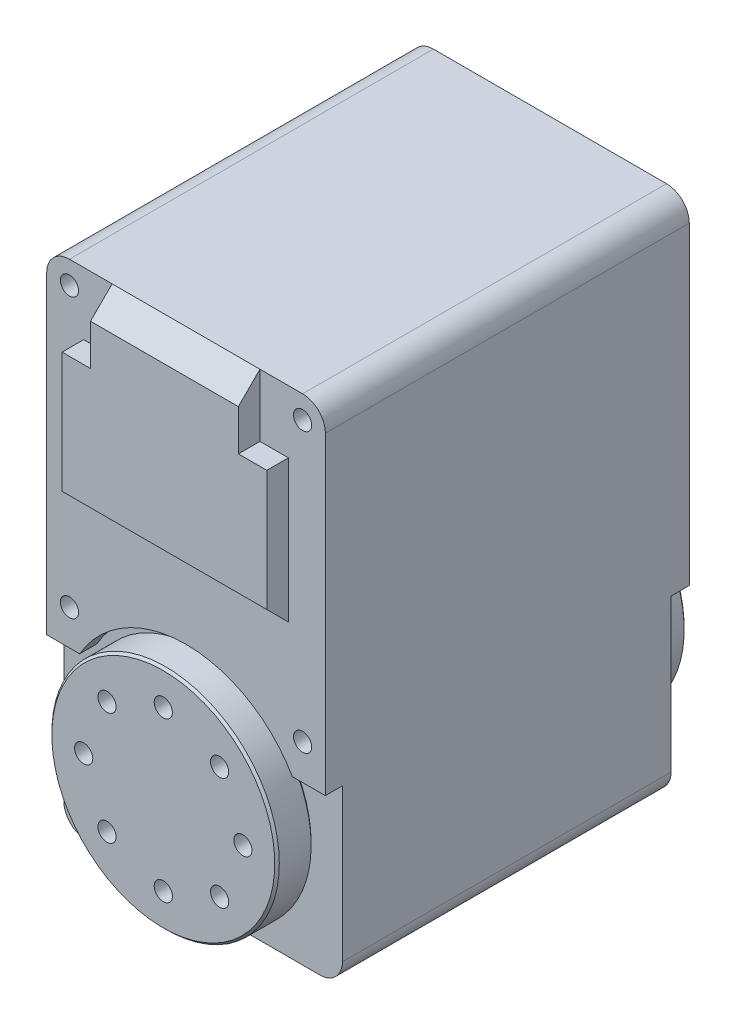
SolidWorks part; units mm, degrees
ref_plane "Front Plane" through (0, 0, 0) normal (0, 0, 1) x (1, 0, 0)
ref_plane "Top Plane" through (0, 0, 0) normal (0, 1, 0) x (1, 0, 0)
ref_plane "Right Plane" through (0, 0, 0) normal (1, 0, 0) x (0, 0, -1)
sketch "Sketch1" plane through (0, 0, 0) normal (0, 0, 1) x (1, 0, 0)
  line L1 (-10.25, 22.5) -> (10.25, 22.5)
  line L2 (-12.25, 20.5) -> (-12.25, -20.5)
  line L3 (-10.25, -22.5) -> (10.25, -22.5)
  line L4 (12.25, 20.5) -> (12.25, -20.5)
  line L5 (-12.25, 22.5) -> (12.25, -22.5) construction
  line L6 (-12.25, -22.5) -> (12.25, 22.5) construction
  arc A0 (10.25, -22.5) -> (12.25, -20.5) centre (10.25, -20.5) ccw
  arc A1 (-10.25, -22.5) -> (-12.25, -20.5) centre (-10.25, -20.5) cw
  arc A2 (12.25, 20.5) -> (10.25, 22.5) centre (10.25, 20.5) ccw
  arc A3 (-12.25, 20.5) -> (-10.25, 22.5) centre (-10.25, 20.5) cw
  point P0 (0, 0)
  dimension "D3" = 2
  dimension "D1" = 24.5
  dimension "D2" = 45
extrude "Boss-Extrude1" add sketch "Sketch1" along normal blind 32
sketch "Sketch2" plane through (0, 0, 32) normal (0, 0, 1) x (1, 0, 0)
  line L0 (-10.25, -22.5) -> (10.25, -22.5) construction
  line L1 (12.25, -20.5) -> (12.25, 20.5) construction
  line L2 (-12.25, 20.5) -> (-12.25, -20.5) construction
  line L3 (-12.25, -7.1) -> (12.25, -7.1)
  line L4 (-12.25, -7.1) -> (-12.25, -22.5)
  line L5 (-12.25, -22.5) -> (12.25, -22.5)
  line L6 (12.25, -7.1) -> (12.25, -22.5)
  circle A0 centre (0, -12.5) radius 10.8
  arc M5 (10.25, -22.5) -> (12.25, -20.5) centre (10.25, -20.5) ccw
  line M6 (12.25, -20.5) -> (12.25, 20.5)
  line M10 (-12.25, 20.5) -> (-12.25, -20.5)
  arc M11 (-12.25, -20.5) -> (-10.25, -22.5) centre (-10.25, -20.5) ccw
  line M12 (-10.25, -22.5) -> (10.25, -22.5)
  dimension "D1" = 21.6
  dimension "D2" = 10
  dimension "D3" = 12.25
  dimension "D4" = 0
  dimension "D5" = 0
  dimension "D6" = 15.4
extrude "Cut-Extrude1" cut sketch "Sketch2" against normal blind 1.5 contours L3 A0 | L3 A0 L5 | A0 L3 M12 M5 M6 | A0 L3 M10 M11 M12 region at (-10.3353, -16.6231, 32) region at (0, -4.8858, 32) region at (0, -14.2224, 32) region at (10.3353, -16.6231, 32)
sketch "Sketch3" plane through (0, 0, 0) normal (0, 0, -1) x (-1, 0, 0)
  line L0 (10.25, -22.5) -> (-10.25, -22.5) construction
  line L1 (12.25, 20.5) -> (12.25, -20.5) construction
  line L3 (-12.25, -7.1) -> (12.25, -7.1)
  line L4 (-12.25, -7.1) -> (-12.25, -22.5)
  line L5 (-12.25, -22.5) -> (12.25, -22.5)
  line L6 (12.25, -7.1) -> (12.25, -22.5)
  circle A0 centre (0, -12.5) radius 10.8
  dimension "D1" = 21.6
  dimension "D2" = 10
  dimension "D3" = 12.25
  dimension "D4" = 0
  dimension "D5" = 0
extrude "Cut-Extrude2" cut sketch "Sketch3" against normal blind 1.6 contours L3 A0 | L3 A0 L5 | L4 L5 L6 L3 region at (0, -4.8858, 0) region at (0, -14.2224, 0)
sketch "Sketch4" plane through (0, 0, 30.5) normal (0, 0, 1) x (1, 0, 0)
  circle A0 centre (0, -12.5) radius 3.2
  dimension "D1" = 6.4
extrude "Boss-Extrude2" add sketch "Sketch4" along normal blind 0.3 and the other way blind 29.3
sketch "Sketch5" plane through (0, 0, 30.8) normal (0, 0, 1) x (1, 0, 0)
  line L0 (12.25, -20.5) -> (12.25, -7.1) construction
  circle A0 centre (0, -12.5) radius 10
  circle A1 centre (0, -5.5) radius 0.8
  circle A2 centre (4.9497, -7.5503) radius 0.8
  circle A3 centre (7, -12.5) radius 0.8
  circle A4 centre (4.9497, -17.4497) radius 0.8
  circle A5 centre (0, -19.5) radius 0.8
  circle A6 centre (-4.9497, -17.4497) radius 0.8
  circle A7 centre (-7, -12.5) radius 0.8
  circle A8 centre (-4.9497, -7.5503) radius 0.8
  point P24 (0, -12.5)
  dimension "D1" = 20
  dimension "D2" = 1.6
  dimension "D3" = 7
  dimension "D6" = 7
  dimension "D7" = 7
  dimension "D4" = 12.25
  dimension "D5" = 8
extrude "Boss-Extrude3" add sketch "Sketch5" along normal blind 3.2
sketch "Sketch6" plane through (0, 0, 1.2) normal (0, 0, -1) x (-1, 0, 0)
  line L0 (12.25, 20.5) -> (12.25, -7.1) construction
  circle A0 centre (0, -12.5) radius 10
  circle A1 centre (0, -5.5) radius 0.8
  circle A2 centre (4.9497, -7.5503) radius 0.8
  circle A3 centre (7, -12.5) radius 0.8
  circle A4 centre (4.9497, -17.4497) radius 0.8
  circle A5 centre (0, -19.5) radius 0.8
  circle A6 centre (-4.9497, -17.4497) radius 0.8
  circle A7 centre (-7, -12.5) radius 0.8
  circle A8 centre (-4.9497, -7.5503) radius 0.8
  point P23 (0, -12.5)
  dimension "D1" = 20
  dimension "D2" = 1.6
  dimension "D3" = 7
  dimension "D4" = 12.25
  dimension "D5" = 8
extrude "Boss-Extrude5" add sketch "Sketch6" along normal blind 3.2
sketch "Sketch7" plane through (0, 0, 32) normal (0, 0, 1) x (1, 0, 0)
  line L0 (10.25, 22.5) -> (-10.25, 22.5) construction
  line L1 (-9, 22.5) -> (9, 22.5)
  line L2 (-9, 22.5) -> (-9, 4.5)
  line L3 (-9, 4.5) -> (9, 4.5)
  line L4 (9, 22.5) -> (9, 4.5)
  line L6 (-9, 22.5) -> (-6.5, 22.5)
  line L7 (-9, 22.5) -> (-9, 17)
  line L8 (-9, 17) -> (-6.5, 17)
  line L9 (-6.5, 22.5) -> (-6.5, 17)
  line L10 (9, 22.5) -> (6.5, 22.5)
  line L11 (9, 22.5) -> (9, 17)
  line L12 (9, 17) -> (6.5, 17)
  line L13 (6.5, 22.5) -> (6.5, 17)
  dimension "D1" = 18
  dimension "D2" = 9
  dimension "D3" = 18
  dimension "D4" = 5.5
  dimension "D5" = 5.5
  dimension "D6" = 2.5
  dimension "D7" = 2.5
extrude "Boss-Extrude6" add sketch "Sketch7" along normal blind 1.9 contours L13 L1 L9 L8 L2 L3 L4 L12 region at (0, 12.9203, 32)
chamfer "Chamfer1" distance 1.9 angle 45 2 edges at (0, 22.5, 33.9) (0, 4.5, 33.9)
sketch "Sketch8" plane through (0, 0, 0) normal (0, 0, -1) x (-1, 0, 0)
  line L0 (-10.25, 22.5) -> (10.25, 22.5) construction
  line L1 (-7, 22.5) -> (7, 22.5)
  line L2 (-7, 22.5) -> (-7, -7.5)
  line L3 (-7, -7.5) -> (7, -7.5)
  line L4 (7, 22.5) -> (7, -7.5)
  circle A0 centre (0, -12.5) radius 10.8
  arc M4 (-9.3531, -7.1) -> (9.3531, -7.1) centre (0, -12.5) cw
  line M8 (10.25, 22.5) -> (-10.25, 22.5)
  dimension "D4" = 21.6
  dimension "D1" = 14
  dimension "D2" = 7
  dimension "D3" = 30
extrude "Boss-Extrude7" add sketch "Sketch8" along normal blind 1.1 contours L4 L2 M8 M4 region at (0, 9.9823, 0)
chamfer "Chamfer2" distance 1.1 angle 45 1 edges at (0, 22.5, -1.1)
sketch "Sketch9" plane through (0, 0, 32) normal (0, 0, 1) x (1, 0, 0)
  line L0 (10.25, 22.5) -> (6.5, 22.5) construction
  line L1 (-6.5, 22.5) -> (-10.25, 22.5) construction
  line L2 (-12.25, 20.5) -> (-12.25, -7.1) construction
  line L3 (12.25, -7.1) -> (12.25, 20.5) construction
  circle A0 centre (-10.25, 20.5) radius 0.8
  circle A1 centre (10.25, 20.5) radius 0.8
  circle A2 centre (-10.25, -4) radius 0.8
  circle A3 centre (10.25, -4) radius 0.8
  dimension "D1" = 20.5
  dimension "D2" = 1.6
  dimension "D3" = 1.6
  dimension "D4" = 2
  dimension "D5" = 2
  dimension "D6" = 2
  dimension "D7" = 1.6
  dimension "D8" = 1.6
  dimension "D9" = 24.5
  dimension "D10" = 24.5
  dimension "D11" = 2
  dimension "D12" = 2
extrude "Cut-Extrude3" cut sketch "Sketch9" against normal offset from surface (3 mm away) 3 up to face at (0, 11.6143, 32)
sketch "Sketch10" plane through (0, 0, 0) normal (0, 0, -1) x (-1, 0, 0)
  line L0 (-12.25, -7.1) -> (-12.25, 20.5) construction
  line L1 (-10.25, 22.5) -> (-7, 22.5) construction
  line L2 (7, 22.5) -> (10.25, 22.5) construction
  line L3 (12.25, 20.5) -> (12.25, -7.1) construction
  circle A0 centre (-10.25, 20.5) radius 0.8
  circle A1 centre (10.25, 20.5) radius 0.8
  circle A2 centre (-10.25, -4) radius 0.8
  circle A3 centre (10.25, -4) radius 0.8
  dimension "D1" = 2
  dimension "D2" = 2
  dimension "D3" = 2
  dimension "D4" = 2
  dimension "D5" = 1.6
  dimension "D6" = 1.6
  dimension "D7" = 1.6
  dimension "D8" = 1.6
  dimension "D9" = 24.5
  dimension "D10" = 24.5
  dimension "D11" = 2
  dimension "D12" = 2
extrude "Cut-Extrude4" cut sketch "Sketch10" against normal blind 3
chamfer "Chamfer3" distance 0.2 angle 45 4 edges at (10, -12.5, 30.8) (-10, -12.5, 1.2) (-10, -12.5, -2) (10, -12.5, 34)
